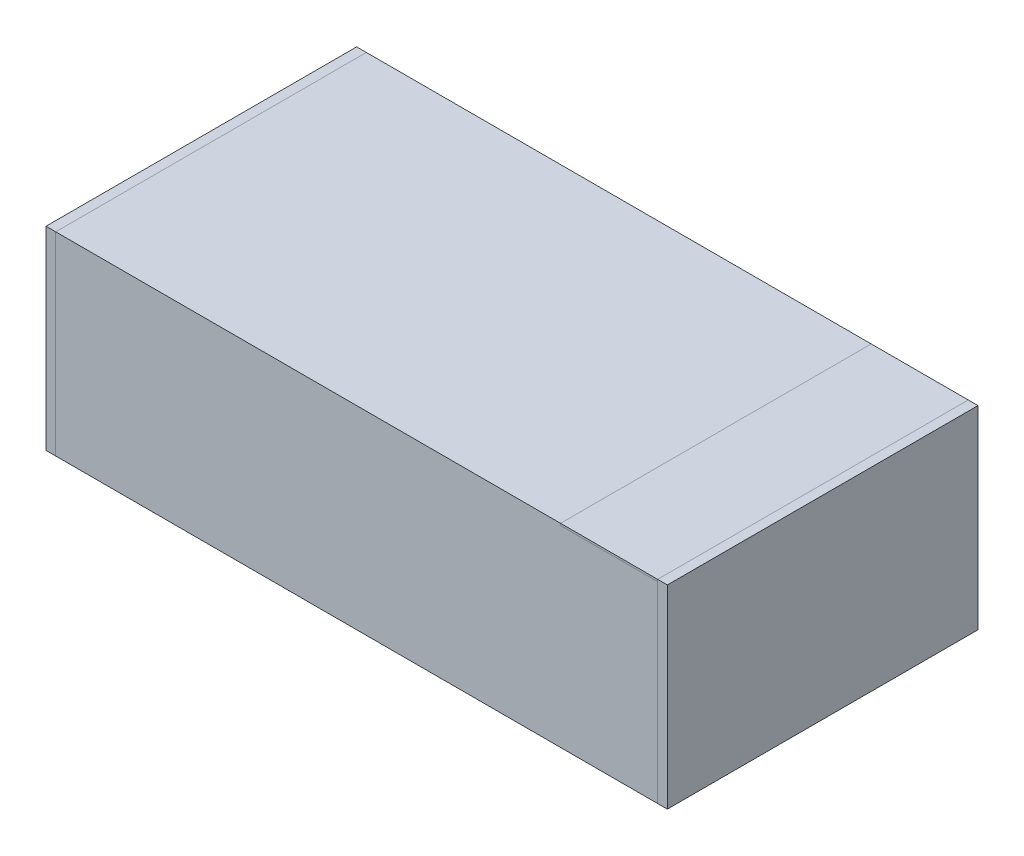
SolidWorks part; units mm, degrees
note: The reader was unsure of these and kept them because the rebuilt part matched: shared geometry of "Sketch2<2>", "Sketch3<2>", "Sketch3<3>", "Sketch3<4>", "Sketch5<2>".
other "ANODE_MARK"
other "PLUS_PIN"
other "MINUS_PIN"
other "BASE"
ref_plane "Front Plane" through (0, 0, 0) normal (0, 0, 1) x (1, 0, 0)
ref_plane "Top Plane" through (0, 0, 0) normal (0, 1, 0) x (1, 0, 0)
ref_plane "Right Plane" through (0, 0, 0) normal (1, 0, 0) x (0, 0, -1)
sketch "Sketch1" plane through (0, 0, 0) normal (0, 1, 0) x (1, 0, 0)
  line L1 (-1.6, -0.8) -> (1.6, -0.8)
  line L2 (-1.6, -0.8) -> (-1.6, 0.8)
  line L3 (-1.6, 0.8) -> (1.6, 0.8)
  line L4 (1.6, -0.8) -> (1.6, 0.8)
  line L5 (-1.6, -0.8) -> (1.6, 0.8) construction
  line L6 (-1.6, 0.8) -> (1.6, -0.8) construction
  point P0 (0, 0)
  dimension "D1" = 3.2
  dimension "D2" = 1.6
extrude "Boss-Extrude1" add sketch "Sketch1" along normal blind 1
sketch "Sketch2" plane through (0, 0, 0) normal (0, 1, 0) x (1, 0, 0)
  line L0 (-0.8, -0.75) -> (-0.8, 0.75)
  line L1 (-1.6, 0.8) -> (-1.6, -0.8) construction
  line L2 (-0.8, -0.75) -> (-1.4, -0.75)
  line L3 (-0.8, 0.75) -> (-1.4, 0.75)
  line L4 (-1.6, -0.8) -> (1.6, -0.8) construction
  line L6 (-1.55, -0.8) -> (-1.55, -0.65)
  line L7 (-1.55, -0.65) -> (-1.4, -0.75)
  line L8 (-1.55, -0.8) -> (-1.6, -0.8)
  line L9 (-1.6, -0.8) -> (-1.6, 0.8)
  line L10 (-1000, 0) -> (49000, 0) construction
  line L11 (0, -1000) -> (0, 49000) construction
  line L12 (-1.55, 0.8) -> (-1.6, 0.8)
  line L13 (-1.55, 0.8) -> (-1.55, 0.65)
  line L14 (-1.55, 0.65) -> (-1.4, 0.75)
  line L15 (1.55, 0.65) -> (1.4, 0.75)
  line L16 (1.55, 0.8) -> (1.55, 0.65)
  line L17 (1.55, 0.8) -> (1.6, 0.8)
  line L18 (1.6, -0.8) -> (1.6, 0.8)
  line L19 (1.55, -0.8) -> (1.6, -0.8)
  line L20 (1.55, -0.65) -> (1.4, -0.75)
  line L21 (1.55, -0.8) -> (1.55, -0.65)
  line L22 (0.8, 0.75) -> (1.4, 0.75)
  line L23 (0.8, -0.75) -> (1.4, -0.75)
  line L24 (0.8, -0.75) -> (0.8, 0.75)
  point P22 (-1.6, 0)
  point P31 (1.6, 0)
  dimension "D1" = 0.8
  dimension "D2" = 0.05
  dimension "D4" = 0.05
  dimension "D5" = 0.15
  dimension "D6" = 0.2
extrude "Cut-Extrude2" cut sketch "Sketch2" along normal blind 0.05
extrude "Boss-Extrude2" add sketch "Sketch2<2>" along normal blind 0.05 separate body
sketch "Sketch2<2>" plane through (0, 0, 0) normal (0, 1, 0) x (1, 0, 0) same geometry as "Sketch2"
sketch "Sketch3" plane through (0, 0, 0) normal (1, 0, 0) x (0, 0, -1)
  line L1 (-0.8, 1) -> (0.8, 1)
  line L2 (-0.8, 1) -> (-0.8, 0.05)
  line L3 (-0.8, 0.05) -> (0.8, 0.05)
  line L4 (0.8, 1) -> (0.8, 0.05)
extrude "Cut-Extrude3" cut sketch "Sketch3" against normal blind 0.05 from surface at 1.6 starting at face at (1.6, 0.525, 0)
extrude "Boss-Extrude3" add sketch "Sketch3<2>" along normal blind 0.05 from vertex
sketch "Sketch3<2>" plane through (0, 0, 0) normal (1, 0, 0) x (0, 0, -1) same geometry as "Sketch3"
extrude "Cut-Extrude4" cut sketch "Sketch3<3>" along normal blind 0.05 from surface at -1.6 starting at face at (-1.6, 0.525, 0)
sketch "Sketch3<3>" plane through (0, 0, 0) normal (1, 0, 0) x (0, 0, -1) same geometry as "Sketch3"
extrude "Boss-Extrude4" add sketch "Sketch3<4>" against normal blind 0.05 from vertex
sketch "Sketch3<4>" plane through (0, 0, 0) normal (1, 0, 0) x (0, 0, -1) same geometry as "Sketch3"
sketch "Sketch5" plane through (0, 0, 0) normal (0, 1, 0) x (1, 0, 0)
  line L0 (-1.55, -0.8) -> (1.55, -0.8) construction
  line L1 (1.55, 0.8) -> (1.05, 0.8)
  line L2 (1.55, 0.8) -> (1.55, -0.8)
  line L3 (1.55, -0.8) -> (1.05, -0.8)
  line L4 (1.05, 0.8) -> (1.05, -0.8)
  dimension "D1" = 0.5
extrude "Cut-Extrude5" cut sketch "Sketch5" against normal blind 0.01 from surface at 1 starting at face at (0, 1, 0)
extrude "Boss-Extrude5" add sketch "Sketch5<2>" along normal blind 0.01 from surface at 0.99 separate body starting at face at (1.3, 0.99, 0)
sketch "Sketch5<2>" plane through (0, 0, 0) normal (0, 1, 0) x (1, 0, 0) same geometry as "Sketch5"
sketch "Sketch6" plane through (0, 1, 0) normal (0, 1, 0) x (1, 0, 0)
  line L0 (1.05, 0.4034) -> (-1.55, 0.4034) construction
  line L1 (1.05, -0.8) -> (1.05, 0.8) construction
  line L2 (-1.55, 0.8) -> (-1.55, -0.8) construction
  text T0 "J476" font "Century Gothic" height 0.7
extrude "Boss-Extrude6" [suppressed] add sketch "Sketch6" along normal blind 0.005 separate body
